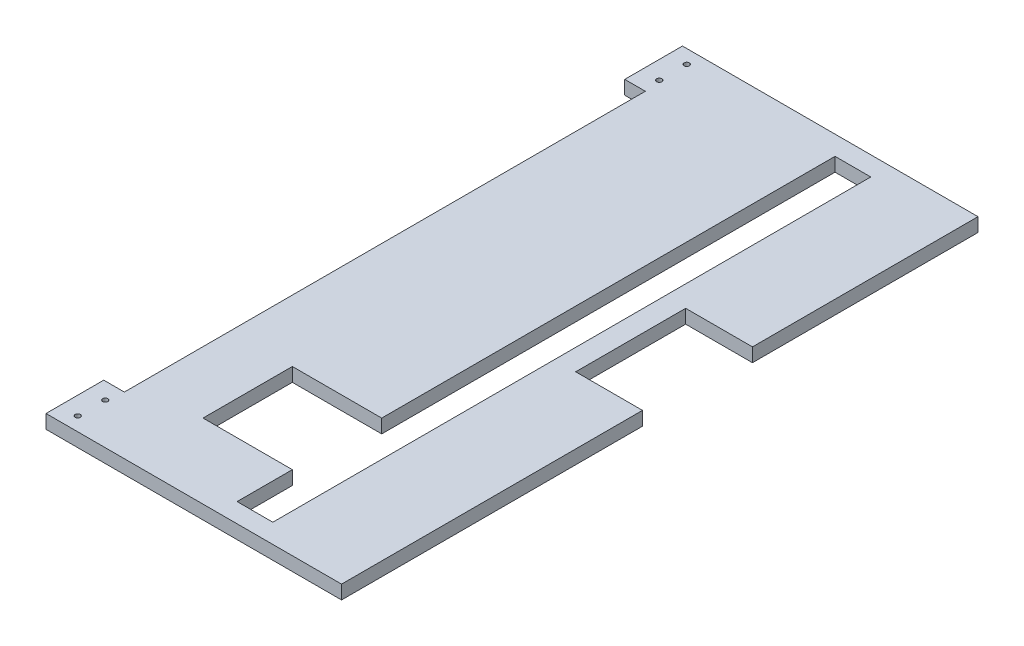
SolidWorks part; units mm, degrees
ref_plane "Front Plane" through (0, 0, 0) normal (0, 0, 1) x (1, 0, 0)
ref_plane "Top Plane" through (0, 0, 0) normal (0, 1, 0) x (1, 0, 0)
ref_plane "Right Plane" through (0, 0, 0) normal (1, 0, 0) x (0, 0, -1)
sketch "Sketch1" plane through (0, 0, 0) normal (0, 1, 0) x (1, 0, 0)
  line L1 (5911.0841, -8489.3124) -> (6341.0841, -8489.3124)
  line L2 (5911.0841, -8489.3124) -> (5911.0841, -8952.3124)
  line L3 (5911.0841, -8952.3124) -> (6341.0841, -8952.3124)
  line L4 (6341.0841, -8489.3124) -> (6341.0841, -8952.3124)
  dimension "D1" = 463
  dimension "D2" = 430
extrude "Boss-Extrude1" add sketch "Sketch1" along normal blind 10
sketch "Sketch2" plane through (0, 10, 0) normal (0, 1, 0) x (1, 0, 0)
  line L0 (5911.0841, -8489.3124) -> (5911.0841, -8952.3124) construction
  line L1 (5959.6841, -8733.0598) -> (5911.0841, -8733.0598)
  line L2 (5959.6841, -8733.0598) -> (5959.6841, -8653.0598)
  line L3 (5959.6841, -8653.0598) -> (5911.0841, -8653.0598)
  line L4 (5911.0841, -8733.0598) -> (5911.0841, -8653.0598)
  line L9 (6341.0841, -8952.3124) -> (6341.0841, -8489.3124) construction
  line L10 (6341.0841, -8733.3844) -> (6292.4841, -8733.3844)
  line L11 (6341.0841, -8733.3844) -> (6341.0841, -8653.3844)
  line L12 (6341.0841, -8653.3844) -> (6292.4841, -8653.3844)
  line L13 (6292.4841, -8733.3844) -> (6292.4841, -8653.3844)
  dimension "D1" = 48.6
  dimension "D2" = 80
  dimension "D3" = 80
  dimension "D4" = 48.6
extrude "Cut-Extrude1" cut sketch "Sketch2" against normal blind 10
sketch "Sketch3" plane through (0, 10, 0) normal (0, 1, 0) x (1, 0, 0)
  line L0 (5975.0841, -8541.6519) -> (5975.0841, -8938.3124)
  line L1 (6277.0841, -8938.3124) -> (6251.0841, -8938.3124)
  line L2 (6277.0841, -8938.3124) -> (6277.0841, -8503.3124)
  line L3 (6277.0841, -8503.3124) -> (6251.0841, -8503.3124)
  line L4 (6251.0841, -8938.3124) -> (6251.0841, -8503.3124)
  line L5 (5975.0841, -8503.3124) -> (6001.0841, -8503.3124)
  line L11 (5975.0841, -8938.3124) -> (6001.0841, -8938.3124)
  line L12 (6001.0841, -8503.3124) -> (6001.0841, -8938.3124)
  line L33 (5946.4841, -8529.3124) -> (5969.1312, -8529.3124)
  line L34 (5946.4841, -8529.3124) -> (5946.4841, -8569.3124)
  line L35 (5946.4841, -8569.3124) -> (5969.1312, -8569.3124)
  line L36 (5911.0841, -8733.0598) -> (5911.0841, -8952.3124) construction
  line L37 (6341.0841, -8952.3124) -> (6341.0841, -8733.3844) construction
  line L38 (5969.1312, -8529.3124) -> (5969.1312, -8569.3124)
  line L39 (6111.0841, -8531.3124) -> (6141.0841, -8531.3124)
  line L40 (6111.0841, -8531.3124) -> (6111.0841, -8910.3124)
  line L41 (6111.0841, -8910.3124) -> (6141.0841, -8910.3124)
  line L42 (6141.0841, -8531.3124) -> (6141.0841, -8910.3124)
  line L44 (6341.0841, -8489.3124) -> (5911.0841, -8489.3124) construction
  line L45 (5975.0841, -8503.3124) -> (5975.0841, -8541.6519)
  line L47 (5911.0841, -8952.3124) -> (6341.0841, -8952.3124) construction
  circle A0 centre (6112.9841, -8942.3124) radius 1.9
  circle A1 centre (6139.1841, -8942.3124) radius 1.9
  circle A2 centre (6112.9841, -8499.3124) radius 1.9
  circle A3 centre (6139.1841, -8499.3124) radius 1.9
  circle A4 centre (6112.9841, -8922.3124) radius 1.9
  circle A5 centre (6139.1841, -8922.3124) radius 1.9
  circle A6 centre (6112.9841, -8519.3124) radius 1.9
  circle A7 centre (6139.1841, -8519.3124) radius 1.9
  point P32 (6126.0841, -8489.3124)
  point P33 (6126.0841, -8531.3124)
  dimension "D12" = 10
  dimension "D13" = 10
  dimension "D15" = 42
  dimension "D16" = 20
  dimension "D18" = 20
  dimension "D1" = 26
  dimension "D2" = 435
  dimension "D3" = 26
  dimension "D4" = 435
  dimension "D5" = 10
  dimension "D6" = 64
  dimension "D7" = 40
  dimension "D8" = 64
  dimension "D9" = 30
  dimension "D10" = 379
  dimension "D11" = 110
  dimension "D14" = 10
  dimension "D17" = 20
  dimension "D19" = 20
  dimension "D20" = 14
  dimension "D21" = 14
extrude "Cut-Extrude2" cut sketch "Sketch3" against normal blind 10
sketch "Sketch4" plane through (0, 10, 0) normal (0, 1, 0) x (1, 0, 0)
  line L0 (6251.0841, -8503.3124) -> (6251.0841, -8938.3124) construction
  line L1 (6251.0841, -8898.0965) -> (6186.0841, -8898.0965)
  line L2 (6251.0841, -8898.0965) -> (6251.0841, -8833.0965)
  line L3 (6251.0841, -8833.0965) -> (6186.0841, -8833.0965)
  line L4 (6186.0841, -8898.0965) -> (6186.0841, -8833.0965)
  dimension "D1" = 65
  dimension "D2" = 65
extrude "Cut-Extrude3" cut sketch "Sketch4" against normal blind 10
ref_plane "Plane1" through (6126.0841, 0, 0) normal (-1, 0, 0) x (0, 0, 1)
sketch "Sketch5" plane through (6126.0841, 0, 0) normal (-1, 0, 0) x (0, 0, 1)
  line L1 (8395.6862, 142.8464) -> (9031.9061, 142.8464)
  line L2 (8395.6862, 142.8464) -> (8395.6862, -229.0644)
  line L3 (8395.6862, -229.0644) -> (9031.9061, -229.0644)
  line L4 (9031.9061, 142.8464) -> (9031.9061, -229.0644)
extrude "Cut-Extrude5" cut sketch "Sketch5" along normal blind 255
